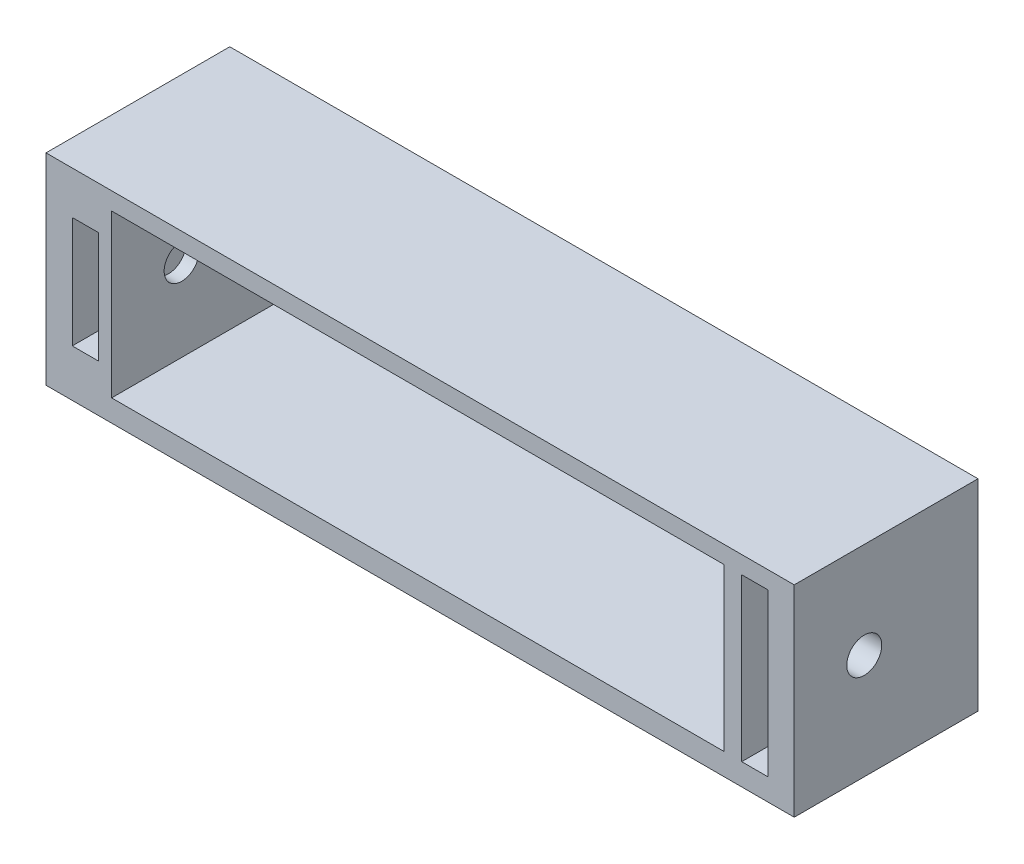
SolidWorks part; units mm, degrees
ref_plane "前基準面" through (0, 0, 0) normal (0, 0, 1) x (1, 0, 0)
ref_plane "上基準面" through (0, 0, 0) normal (0, 1, 0) x (1, 0, 0)
ref_plane "右基準面" through (0, 0, 0) normal (1, 0, 0) x (0, 0, -1)
sketch "草圖1" plane through (0, 0, 0) normal (0, 0, 1) x (1, 0, 0)
  line L0 (25.3269, 9.25) -> (34.5, 9.25)
  line L1 (37.5, -9.25) -> (-37.5, -9.25)
  line L2 (37.5, -9.25) -> (37.5, 9.25)
  line L3 (37.5, 9.25) -> (-37.5, 9.25)
  line L4 (-37.5, -9.25) -> (-37.5, 9.25)
  line L5 (0, 9.25) -> (0, -9.25) construction
  line L6 (37.5, 0) -> (-37.5, 0) construction
  line L7 (34.5, 9.25) -> (34.5, -9.25)
  line L8 (32.5, 9.25) -> (32.5, -9.25)
  line L10 (-36, -6.3557) -> (-39, -6.3557)
  line L12 (-36, 6.3557) -> (-39, 6.3557)
  line L13 (-39, -6.3557) -> (-39, 6.3557)
  line L14 (-37.5, 6.3557) -> (-37.5, -6.3557) construction
  line L15 (-33, 0) -> (-39, 0) construction
  line L16 (-39, 6.3557) -> (-42, 6.3557)
  line L17 (-39, 6.3557) -> (-39, -6.3557)
  line L18 (-39, -6.3557) -> (-42, -6.3557)
  line L19 (-42, 6.3557) -> (-42, -6.3557)
  line L20 (40.5, -11.75) -> (-45, -11.75)
  line L21 (40.5, -11.75) -> (40.5, 11.25)
  line L22 (40.5, 11.25) -> (-45, 11.25)
  line L23 (-45, -11.75) -> (-45, 11.25)
  point P0 (0, 0)
  dimension "D1" = 70
  dimension "D2" = 2
  dimension "D3" = 3
  dimension "D4" = 1.5
  dimension "D5" = 3
  dimension "D6" = 2
  dimension "D7" = 3
  dimension "D8" = 3
  dimension "D9" = 18.5
  dimension "D10" = 23
extrude "填料-伸長1" add sketch "草圖1" along normal blind 19 contours L23 L20 L21 L22 L19 L16 L12 L3 L0 L2 L1 L10 L18 | L13 L10 L4 L12 | L3 L8 L1 L7 region at (33.5, 0, 0) region at (-38.25, 0, 0) region at (-2.25, -10.8646, 0)
sketch "草圖2" plane through (0, 0, 0) normal (0, 0, -1) x (-1, 0, 0)
  line L0 (-40.5, -11.75) -> (-40.5, 11.25) construction
  line L1 (-40.5, 11.25) -> (45, 11.25)
  line L2 (-40.5, 11.25) -> (-40.5, -11.75)
  line L3 (-40.5, -11.75) -> (45, -11.75)
  line L4 (45, 11.25) -> (45, -11.75)
extrude "填料-伸長2" add sketch "草圖2" along normal blind 2
sketch "草圖3" plane through (40.5, 0, 0) normal (1, 0, 0) x (0, 0, -1)
  line L0 (-19, -11.75) -> (-19, 11.25) construction
  circle A0 centre (-11, 0.283) radius 2
  point P4 (-19, -0.25)
  dimension "D1" = 4
  dimension "D2" = 8
extrude "除料-伸長1" cut sketch "草圖3" against normal blind 97 contours A0
sketch "草圖4" plane through (0, 0, -2) normal (0, 0, -1) x (-1, 0, 0)
  line L0 (45, -11.75) -> (45, 11.25) construction
  line L1 (35, -7.859) -> (-30.5, -7.859)
  line L2 (35, -7.859) -> (35, 7.859)
  line L3 (35, 7.859) -> (-30.5, 7.859)
  line L4 (-30.5, -7.859) -> (-30.5, 7.859)
  line L5 (-0.091, 7.859) -> (-0.091, -7.859) construction
  line L6 (35, 0) -> (-35.1821, 0) construction
  line L7 (-40.5, 11.25) -> (-40.5, -11.75) construction
  dimension "D1" = 10
  dimension "D2" = 10
extrude "除料-伸長2" cut sketch "草圖4" against normal blind 10 contours L3 L4 L1 L2
